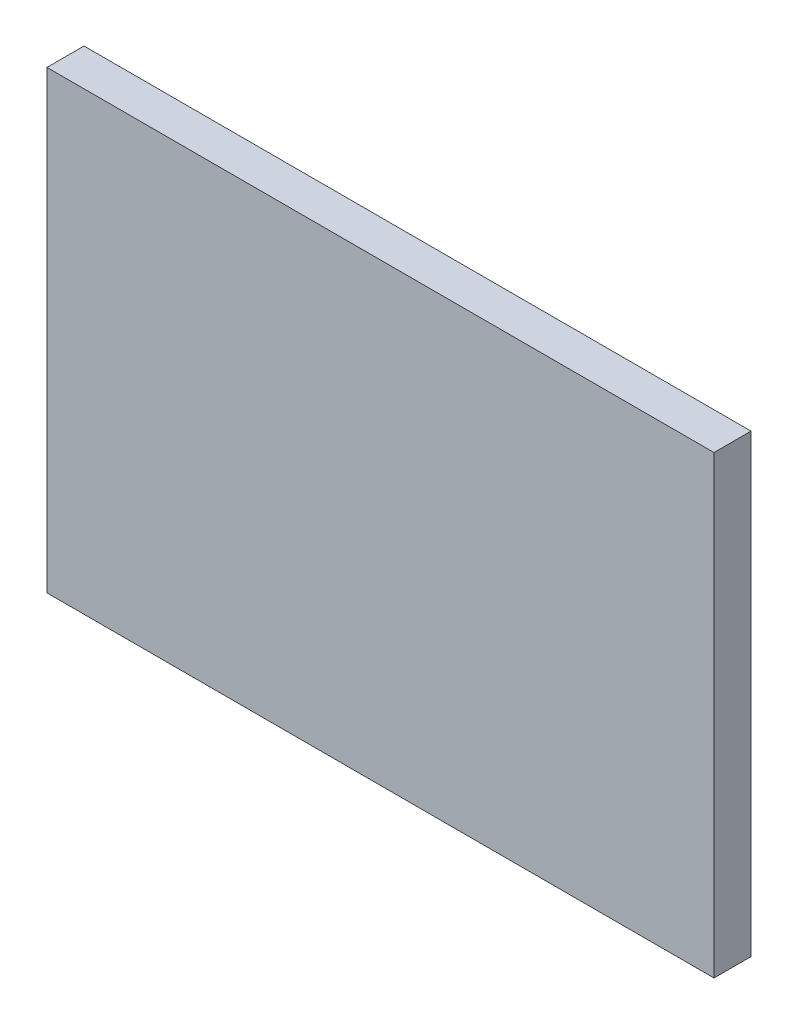
SolidWorks part; units mm, degrees
ref_plane "Front Plane" through (0, 0, 0) normal (0, 0, 1) x (1, 0, 0)
ref_plane "Top Plane" through (0, 0, 0) normal (0, 1, 0) x (1, 0, 0)
ref_plane "Right Plane" through (0, 0, 0) normal (1, 0, 0) x (0, 0, -1)
sketch "Sketch1" plane through (0, 0, 0) normal (0, 0, 1) x (1, 0, 0)
  line L1 (-57.15, 38.989) -> (57.15, 38.989)
  line L2 (-57.15, 38.989) -> (-57.15, -38.989)
  line L3 (-57.15, -38.989) -> (57.15, -38.989)
  line L4 (57.15, 38.989) -> (57.15, -38.989)
  line L5 (-57.15, 38.989) -> (57.15, -38.989) construction
  line L6 (-57.15, -38.989) -> (57.15, 38.989) construction
  point P0 (0, 0)
  dimension "D1" = 114.3
  dimension "D2" = 77.978
extrude "Boss-Extrude1" add sketch "Sketch1" along normal blind 6.35
